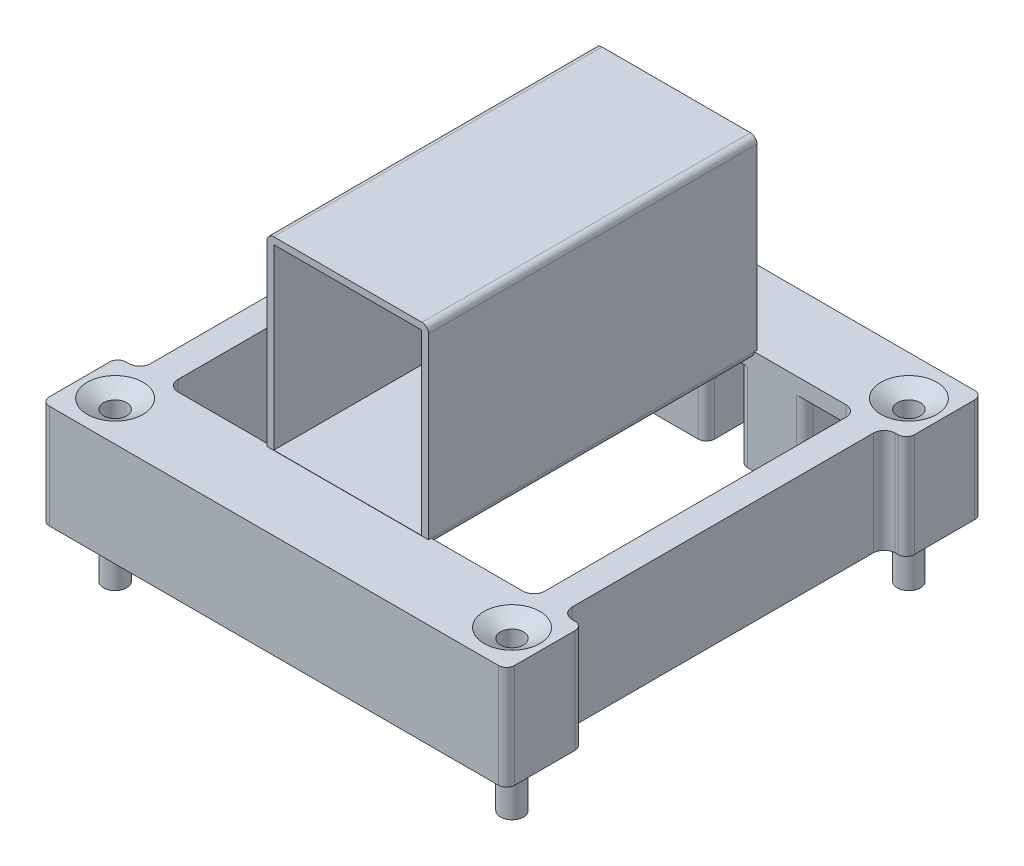
SolidWorks part; units mm, degrees
ref_plane "Front Plane" through (0, 0, 0) normal (0, 0, 1) x (1, 0, 0)
ref_plane "Top Plane" through (0, 0, 0) normal (0, 1, 0) x (1, 0, 0)
ref_plane "Right Plane" through (0, 0, 0) normal (1, 0, 0) x (0, 0, -1)
sketch "Sketch1" plane through (0, 0, 0) normal (0, 0, 1) x (1, 0, 0)
  line L0 (14.75, -16.3) -> (14.75, 16.3) construction
  line L1 (13.55, -17.5) -> (-13.55, -17.5) construction
  line L2 (-14.75, -16.3) -> (-14.75, 16.3) construction
  line L3 (13.55, 17.5) -> (-13.55, 17.5) construction
  line L4 (14.75, -16.3) -> (14.75, 16.3)
  line L5 (13.55, -17.5) -> (-13.55, -17.5)
  line L6 (-14.75, -16.3) -> (-14.75, 16.3)
  line L7 (13.55, 17.5) -> (-13.55, 17.5)
  line L8 (13.5, -16.25) -> (13.5, 16.25) construction
  line L9 (13.5, -16.25) -> (-13.5, -16.25) construction
  line L10 (-13.5, -16.25) -> (-13.5, 16.25) construction
  line L11 (13.5, 16.25) -> (-13.5, 16.25) construction
  line L12 (13.5, -16.25) -> (13.5, 16.25)
  line L13 (13.5, -16.25) -> (-13.5, -16.25)
  line L14 (-13.5, -16.25) -> (-13.5, 16.25)
  line L15 (13.5, 16.25) -> (-13.5, 16.25)
  arc A0 (14.75, 16.3) -> (13.55, 17.5) centre (13.55, 16.3) ccw construction
  arc A1 (13.55, -17.5) -> (14.75, -16.3) centre (13.55, -16.3) ccw construction
  arc A2 (-14.75, -16.3) -> (-13.55, -17.5) centre (-13.55, -16.3) ccw construction
  arc A3 (-13.55, 17.5) -> (-14.75, 16.3) centre (-13.55, 16.3) ccw construction
  arc A4 (14.75, 16.3) -> (13.55, 17.5) centre (13.55, 16.3) ccw
  arc A5 (13.55, -17.5) -> (14.75, -16.3) centre (13.55, -16.3) ccw
  arc A6 (-14.75, -16.3) -> (-13.55, -17.5) centre (-13.55, -16.3) ccw
  arc A7 (-13.55, 17.5) -> (-14.75, 16.3) centre (-13.55, 16.3) ccw
extrude "Boss-Extrude1" add sketch "Sketch1" along normal mid plane 60
sketch "Sketch2" plane through (0, 0, 0) normal (1, 0, 0) x (0, 0, -1)
  line L0 (-29.5, -24.25) -> (-29.5, 24.25) construction
  line L1 (-29.5, -16.3) -> (-43.5, -16.3)
  line L2 (-29.5, -16.3) -> (-29.5, -35.25)
  line L3 (-29.5, -35.25) -> (-43.5, -35.25)
  line L4 (-43.5, -16.3) -> (-43.5, -35.25)
  line L5 (-30, -16.3) -> (30, -16.3) construction
  line L6 (-29.5, -29.25) -> (29.5, -29.25) construction
  line L8 (-43.5, -15.125) -> (-43.5, 15.125) construction
  line L9 (0, 0) -> (0, -45.8115) construction
  line L10 (0, -15.125) -> (0, 15.125) construction
  line L11 (29.5, -35.25) -> (43.5, -35.25)
  line L12 (43.5, -16.3) -> (43.5, -35.25)
  line L13 (29.5, -16.3) -> (43.5, -16.3)
  line L14 (29.5, -16.3) -> (29.5, -35.25)
  dimension "D1" = 6
extrude "Boss-Extrude2" add sketch "Sketch2" along normal mid plane 85
sketch "Sketch3" plane through (0, -35.25, 0) normal (0, -1, 0) x (1, 0, 0)
  line L0 (0, 0) -> (59.8969, 0) construction
  line L1 (42.5, 29.5) -> (-42.5, 29.5) construction
  line L2 (-30, 29.5) -> (-24, 29.5)
  line L3 (-30, 29.5) -> (-30, 39.5)
  line L4 (-30, 39.5) -> (-24, 39.5)
  line L5 (-24, 29.5) -> (-24, 39.5)
  line L6 (-24.25, 29.5) -> (24.25, 29.5) construction
  line L7 (-12, 29.5) -> (-6, 29.5)
  line L8 (-12, 29.5) -> (-12, 39.5)
  line L9 (-12, 39.5) -> (-6, 39.5)
  line L10 (-6, 29.5) -> (-6, 39.5)
  line L11 (0, 0) -> (0, 46.5306) construction
  line L12 (30, 39.5) -> (24, 39.5)
  line L13 (24, 29.5) -> (24, 39.5)
  line L14 (30, 29.5) -> (24, 29.5)
  line L15 (30, 29.5) -> (30, 39.5)
  line L16 (12, 39.5) -> (6, 39.5)
  line L17 (6, 29.5) -> (6, 39.5)
  line L18 (12, 29.5) -> (6, 29.5)
  line L19 (12, 29.5) -> (12, 39.5)
  line L20 (12, -29.5) -> (12, -39.5)
  line L21 (12, -29.5) -> (6, -29.5)
  line L22 (6, -29.5) -> (6, -39.5)
  line L23 (12, -39.5) -> (6, -39.5)
  line L24 (30, -29.5) -> (30, -39.5)
  line L25 (30, -29.5) -> (24, -29.5)
  line L26 (24, -29.5) -> (24, -39.5)
  line L27 (30, -39.5) -> (24, -39.5)
  line L28 (-6, -29.5) -> (-6, -39.5)
  line L29 (-12, -39.5) -> (-6, -39.5)
  line L30 (-12, -29.5) -> (-12, -39.5)
  line L31 (-12, -29.5) -> (-6, -29.5)
  line L32 (-24, -29.5) -> (-24, -39.5)
  line L33 (-30, -39.5) -> (-24, -39.5)
  line L34 (-30, -29.5) -> (-30, -39.5)
  line L35 (-30, -29.5) -> (-24, -29.5)
  dimension "D1" = 12
  dimension "D2" = 12
  dimension "D3" = 6
  dimension "D4" = 6
  dimension "D5" = 10
extrude "Cut-Extrude1" cut sketch "Sketch3" against normal blind 16
fillet "Fillet1" radius 1.49 40 edges at (-24, -27.25, -39.5) (-6, -27.25, -39.5) (12, -27.25, -39.5) (30, -27.25, -39.5) (42.5, -25.775, -29.5) (42.5, -25.775, -43.5) (-42.5, -25.775, -43.5) (-42.5, -25.775, -29.5) (-30, -27.25, -29.5) (-30, -27.25, -39.5) (-24, -27.25, -29.5) (-12, -27.25, -29.5) (-12, -27.25, -39.5) (-6, -27.25, -29.5) (6, -27.25, -29.5) (6, -27.25, -39.5) (12, -27.25, -29.5) (24, -27.25, -29.5) (24, -27.25, -39.5) (30, -27.25, -29.5) (24, -27.25, 39.5) (6, -27.25, 39.5) (-12, -27.25, 39.5) (-30, -27.25, 39.5) (42.5, -25.775, 43.5) (42.5, -25.775, 29.5) (30, -27.25, 29.5) (30, -27.25, 39.5) (24, -27.25, 29.5) (12, -27.25, 29.5) (12, -27.25, 39.5) (6, -27.25, 29.5) (-6, -27.25, 29.5) (-6, -27.25, 39.5) (-12, -27.25, 29.5) (-24, -27.25, 29.5) (-24, -27.25, 39.5) (-30, -27.25, 29.5) (-42.5, -25.775, 43.5) (-42.5, -25.775, 29.5)
sketch "Sketch4" plane through (0, -16.3, 0) normal (0, 1, 0) x (1, 0, 0)
  line L0 (0, 0) -> (38.8928, 0) construction
  line L1 (-36.25, 36.25) -> (36.25, 36.25) construction
  line L2 (-36.25, 36.25) -> (-36.25, -36.25) construction
  line L3 (-36.25, -36.25) -> (36.25, -36.25) construction
  line L4 (36.25, 36.25) -> (36.25, -36.25) construction
  line L5 (-36.25, 36.25) -> (36.25, -36.25) construction
  line L6 (-36.25, -36.25) -> (36.25, 36.25) construction
  line L7 (0, 0) -> (0, -47.3346) construction
  circle A0 centre (36.25, -36.25) radius 2.1
  circle A1 centre (-36.25, -36.25) radius 2.1
  circle A2 centre (-36.25, 36.25) radius 2.1
  circle A3 centre (36.25, 36.25) radius 2.1
  point P0 (0, 0)
  dimension "D3" = 4.2
  dimension "D1" = 72.5
  dimension "D2" = 72.5
extrude "Cut-Extrude2" cut sketch "Sketch4" against normal through all both and the other way through all
chamfer "Chamfer1" distance 3 angle 30 4 edges at (36.25, -16.3, -38.35) (-36.25, -16.3, -38.35) (-36.25, -16.3, 34.15) (36.25, -16.3, 34.15) first distance on face at (36.25, -16.3, -38.35) first distance on face at (-36.25, -16.3, 34.15)
sketch "Sketch5" plane through (0, 0, -29.5) normal (0, 0, 1) x (1, 0, 0)
  line L0 (-14.75, -16.3) -> (-41.01, -16.3) construction
  line L1 (-38.5, -16.3) -> (-33.5, -16.3)
  line L2 (-38.5, -16.3) -> (-38.5, -35.25)
  line L3 (-38.5, -35.25) -> (-33.5, -35.25)
  line L4 (-33.5, -16.3) -> (-33.5, -35.25)
  line L5 (-31.49, -35.25) -> (-41.01, -35.25) construction
  line L6 (-42.5, -35.25) -> (-42.5, -16.3) construction
  line L7 (0, 0) -> (0, -37.6996) construction
  line L8 (33.5, -16.3) -> (33.5, -35.25)
  line L9 (38.5, -35.25) -> (33.5, -35.25)
  line L10 (38.5, -16.3) -> (38.5, -35.25)
  line L11 (38.5, -16.3) -> (33.5, -16.3)
  dimension "D1" = 4
  dimension "D2" = 5
extrude "Boss-Extrude3" add sketch "Sketch5" along normal up to surface (59 mm away) up to face at (0, -25.2999, 29.5)
fillet "Fillet2" radius 2 8 edges at (33.5, -25.775, 29.5) (38.5, -25.775, 29.5) (33.5, -25.775, -29.5) (38.5, -25.775, -29.5) (-38.5, -25.775, -29.5) (-33.5, -25.775, -29.5) (-33.5, -25.775, 29.5) (-38.5, -25.775, 29.5)
sketch "Sketch6" plane through (0, -35.25, 0) normal (0, -1, 0) x (1, 0, 0)
  circle A0 centre (-36.25, 36.25) radius 2.1 construction
  circle A1 centre (36.25, 36.25) radius 2.1 construction
  circle A2 centre (36.25, -36.25) radius 2.1 construction
  circle A3 centre (-36.25, -36.25) radius 2.1 construction
  circle A4 centre (-36.25, 36.25) radius 2.1
  circle A5 centre (36.25, 36.25) radius 2.1
  circle A6 centre (36.25, -36.25) radius 2.1
  circle A7 centre (-36.25, -36.25) radius 2.1
extrude "Boss-Extrude4" add sketch "Sketch6" along normal blind 10 and the other way blind 10 separate body
